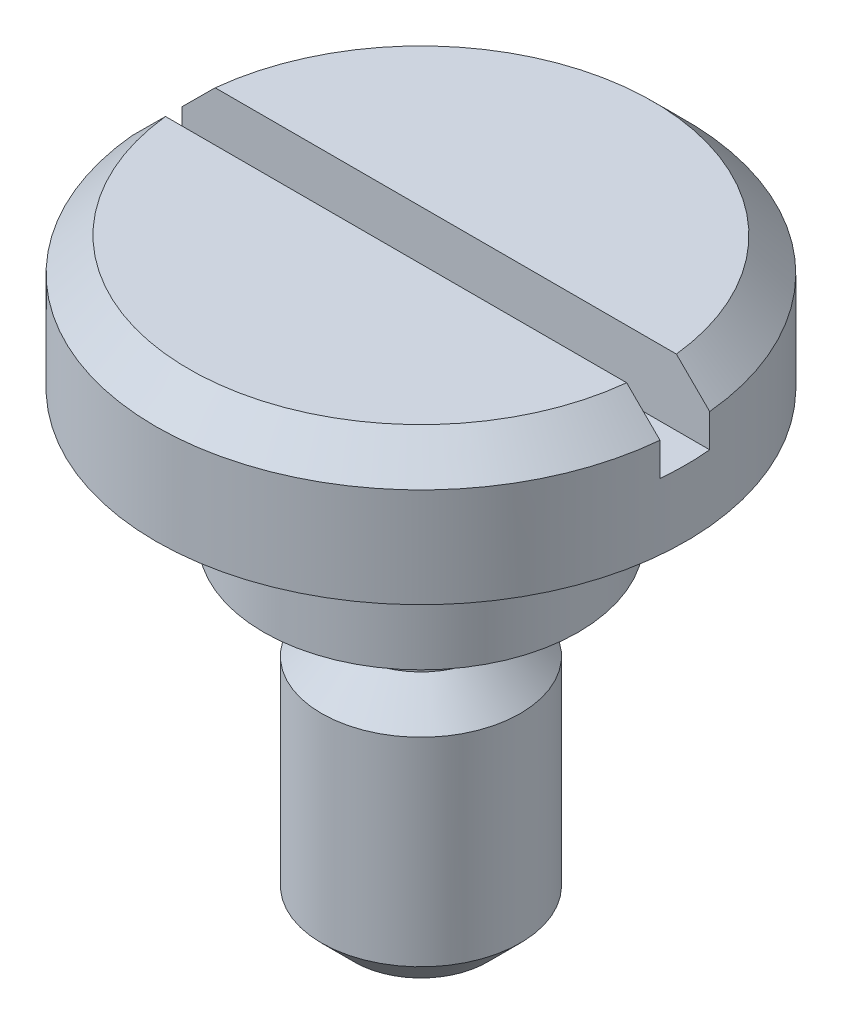
SolidWorks part; units mm, degrees
material "AISI 1045 钢，冷拔"
ref_plane "前视基准面" through (0, 0, 0) normal (0, 0, 1) x (1, 0, 0)
ref_plane "上视基准面" through (0, 0, 0) normal (0, 1, 0) x (1, 0, 0)
ref_plane "右视基准面" through (0, 0, 0) normal (1, 0, 0) x (0, 0, -1)
sketch "草图1" plane through (0, 0, 0) normal (0, 0, 1) x (1, 0, 0)
  line L0 (0, 0) -> (3, 0)
  line L1 (3, 0) -> (3, 8)
  line L2 (3, 8) -> (2, 8)
  line L3 (2, 8) -> (2, 10)
  line L4 (2, 10) -> (4.75, 10)
  line L5 (4.75, 10) -> (4.75, 14)
  line L6 (4.75, 14) -> (8, 14)
  line L7 (8, 14) -> (8, 18)
  line L8 (8, 18) -> (0, 18)
  line L9 (0, 18) -> (0, 0)
  dimension "D1" = 18
  dimension "D2" = 10
  dimension "D3" = 4
  dimension "D4" = 4.75
  dimension "D5" = 8
  dimension "D6" = 3
  dimension "D7" = 1
  dimension "D8" = 2
revolve "旋转1" add sketch "草图1" angle 360 about L9
chamfer "倒角2" distance 1 angle 45 3 edges at (0, 0, 3) (0, 18, 8) (0, 8, 3)
sketch "草图2" plane through (0, 18, 0) normal (0, 1, 0) x (1, 0, 0)
  line L0 (-7.9648, -0.75) -> (7.9648, -0.75)
  line L1 (-7.9648, 0.75) -> (7.9648, 0.75)
  circle A0 centre (0, 0) radius 8 construction
  arc A1 (-7.9648, 0.75) -> (-7.9648, -0.75) centre (0, 0) ccw
  arc A2 (7.9648, -0.75) -> (7.9648, 0.75) centre (0, 0) ccw
  dimension "D1" = 0.75
  dimension "D2" = 0.75
extrude "切除-拉伸1" cut sketch "草图2" against normal blind 2
